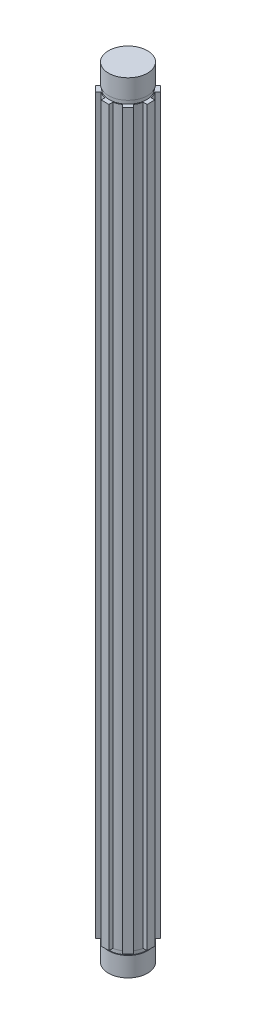
SolidWorks part; units mm, degrees
material "PE High Density"
ref_plane "Front Plane" through (0, 0, 0) normal (0, 0, 1) x (1, 0, 0)
ref_plane "Top Plane" through (0, 0, 0) normal (0, 1, 0) x (1, 0, 0)
ref_plane "Right Plane" through (0, 0, 0) normal (1, 0, 0) x (0, 0, -1)
sketch "Sketch3" plane through (0, 0, 0) normal (1, 0, 0) x (0, 0, -1)
  line L0 (0, 100) -> (5, 100) construction
  line L1 (0, 0) -> (5, 0)
  line L2 (0, 0) -> (0, 200)
  line L3 (0, 200) -> (5, 200)
  line L4 (5, 0) -> (5, 200)
  line L5 (5, 5) -> (4.8, 5)
  line L6 (5, 5) -> (5, 6)
  line L7 (5, 6) -> (4.8, 6)
  line L8 (4.8, 5) -> (4.8, 6)
  line L13 (4.8, 195) -> (4.8, 194)
  line L14 (5, 194) -> (4.8, 194)
  line L15 (5, 195) -> (5, 194)
  line L16 (5, 195) -> (4.8, 195)
  point P6 (5, 185.9235)
  point P12 (0, 0)
  point P13 (5, 203.8903)
  dimension "D1" = 200
  dimension "D2" = 5
  dimension "D3" = 4.8
  dimension "D4" = 1
  dimension "D5" = 5
revolve "Revolve1" add sketch "Sketch3" angle 360 about L2 region at (0, 149.9822, -2.499) region at (0, 50.0178, -2.499)
sketch "Sketch4" plane through (0, 0, 0) normal (0, -1, 0) x (1, 0, 0)
  line L0 (-1, 4.899) -> (-1, 5.899)
  line L1 (-1, 5.899) -> (1, 5.899)
  line L2 (1, 5.899) -> (1, 4.899)
  line L3 (0, 0) -> (0, 15.0182) construction
  circle A0 centre (0, 0) radius 5 construction
  arc A1 (-1, 4.899) -> (1, 4.899) centre (0, 0) cw
  circle M6 centre (0, 0) radius 5
  dimension "D1" = 2
  dimension "D2" = 1
extrude "Boss-Extrude2" add sketch "Sketch4" against normal up to surface (194 mm away) from surface contours A1 L3 L1 L0 | L3 L2 L1 M6 region at (-0.509, 0, 5.4322) region at (0.509, 0, 5.4322) up to face at (0, 194, -4.8) starting at face at (0, 6, -4.8)
pattern_circular "CirPattern1" count 8 over 360 about axis through (0, 0, 0) along (0, -1, 0) of "Boss-Extrude2"
